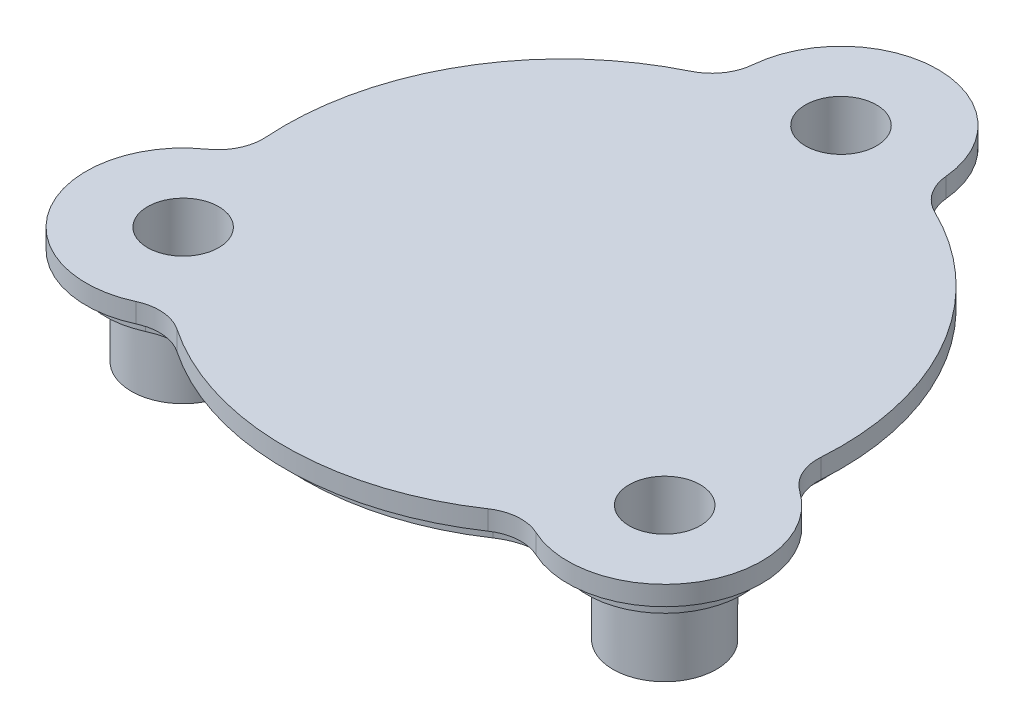
SolidWorks part; units mm, degrees
material "PE Low/Medium Density"
ref_plane "Front Plane" through (0, 0, 0) normal (0, 0, 1) x (1, 0, 0)
ref_plane "Top Plane" through (0, 0, 0) normal (0, 1, 0) x (1, 0, 0)
ref_plane "Right Plane" through (0, 0, 0) normal (1, 0, 0) x (0, 0, -1)
sketch "Sketch1" plane through (0, 0, 0) normal (0, 1, 0) x (1, 0, 0)
  line L0 (0, 0) -> (0, 57) construction
  line L1 (37.2391, 21.5) -> (0, 0) construction
  circle A0 centre (0, 43) radius 5.5
  arc A1 (-14.9415, 44.324) -> (14.9415, 44.324) centre (0, 43) cw
  arc A2 (14.9415, 44.324) -> (18.8462, 38.65) centre (21.9141, 44.9419) ccw
  arc A3 (18.8462, 38.65) -> (37.2391, 21.5) centre (0, 0) cw
  circle A4 centre (0, 43) radius 8
  circle A5 centre (0, 43) radius 3
  arc A6 (-18.8462, 38.65) -> (-37.2391, 21.5) centre (0, 0) ccw
  arc A7 (-14.9415, 44.324) -> (-18.8462, 38.65) centre (-21.9141, 44.9419) cw
  circle A8 centre (37.2391, -21.5) radius 3
  circle A9 centre (37.2391, -21.5) radius 5.5
  circle A10 centre (37.2391, -21.5) radius 8
  arc A11 (45.8564, -9.2223) -> (30.915, -35.1017) centre (37.2391, -21.5) cw
  arc A12 (30.915, -35.1017) -> (24.0488, -35.6462) centre (27.9637, -41.4491) ccw
  arc A13 (45.8564, -9.2223) -> (42.895, -3.0038) centre (49.8779, -3.4927) cw
  arc A14 (42.895, -3.0038) -> (37.2391, 21.5) centre (0, 0) ccw
  arc A15 (24.0488, -35.6462) -> (0, -43) centre (0, 0) cw
  circle A16 centre (-37.2391, -21.5) radius 3
  circle A17 centre (-37.2391, -21.5) radius 5.5
  circle A18 centre (-37.2391, -21.5) radius 8
  arc A19 (-30.915, -35.1017) -> (-45.8564, -9.2223) centre (-37.2391, -21.5) cw
  arc A20 (-45.8564, -9.2223) -> (-42.895, -3.0038) centre (-49.8779, -3.4927) ccw
  arc A21 (-30.915, -35.1017) -> (-24.0488, -35.6462) centre (-27.9637, -41.4491) cw
  arc A22 (-24.0488, -35.6462) -> (0, -43) centre (0, 0) ccw
  arc A23 (-42.895, -3.0038) -> (-37.2391, 21.5) centre (0, 0) cw
  point P65 (0, 0)
  dimension "D1" = 11
  dimension "D2" = 16
  dimension "D3" = 15
  dimension "D4" = 7
  dimension "D8" = 6
  dimension "D9" = 3
extrude "Boss-Extrude1" add sketch "Sketch1" along normal blind 6 contours A17 A16 | A18 A17 | A9 A8 | A10 A9 | A0 A5 | A4 A0 region at (-5.3444, 0, -43) region at (-7.7737, 0, -43) region at (31.8947, 0, 21.5) region at (29.4654, 0, 21.5) region at (-42.5835, 0, 21.5) region at (-45.0128, 0, 21.5)
extrude "Boss-Extrude3" add sketch "Sketch1<4>" against normal blind 3 from offset 18 separate body contours A23 A20 A19 A21 A22 A15 A12 A11 A13 A14 A3 A2 A1 A7 A6 A18 A10 A4 | A18 A17 | A10 A9 | A4 A0 region at (0, 0, 0) region at (-7.7737, 0, -43) region at (29.4654, 0, 21.5) region at (-45.0128, 0, 21.5)
sketch "Sketch1<4>" plane through (0, 0, 0) normal (0, 1, 0) x (1, 0, 0) same geometry as "Sketch1"
extrude "Boss-Extrude2" add sketch "Sketch1<3>" along normal up to surface (18 mm away) contours A18 A17 | A10 A9 | A4 A0 region at (-7.7737, 0, -43) region at (29.4654, 0, 21.5) region at (-45.0128, 0, 21.5) up to face at (0, 18, 0)
sketch "Sketch1<3>" plane through (0, 0, 0) normal (0, 1, 0) x (1, 0, 0) same geometry as "Sketch1"
sketch "Sketch2" plane through (0, 15, 0) normal (0, -1, 0) x (1, 0, 0)
  circle A20 centre (0, -43) radius 8 construction
  circle A21 centre (37.2391, 21.5) radius 8 construction
  circle A22 centre (-37.2391, 21.5) radius 8 construction
  circle A25 centre (0, -43) radius 8
  circle A26 centre (37.2391, 21.5) radius 8
  circle A27 centre (-37.2391, 21.5) radius 8
  arc A40 (-39.9023, 2.7942) -> (-17.5313, -35.9535) centre (0, 0) ccw
  arc A41 (-11.9532, -44.0592) -> (-17.5313, -35.9535) centre (-21.9141, -44.9419) ccw
  arc A42 (-11.9532, -44.0592) -> (11.9532, -44.0592) centre (0, -43) ccw
  arc A43 (17.5313, -35.9535) -> (11.9532, -44.0592) centre (21.9141, -44.9419) ccw
  arc A44 (17.5313, -35.9535) -> (39.9023, 2.7942) centre (0, 0) ccw
  arc A45 (44.133, 11.6779) -> (39.9023, 2.7942) centre (49.8779, 3.4927) ccw
  arc A46 (44.133, 11.6779) -> (32.1798, 32.3813) centre (37.2391, 21.5) ccw
  arc A47 (22.371, 33.1593) -> (32.1798, 32.3813) centre (27.9637, 41.4491) ccw
  arc A48 (22.371, 33.1593) -> (-22.371, 33.1593) centre (0, 0) ccw
  arc A49 (-32.1798, 32.3813) -> (-22.371, 33.1593) centre (-27.9637, 41.4491) ccw
  arc A50 (-32.1798, 32.3813) -> (-44.133, 11.6779) centre (-37.2391, 21.5) ccw
  arc A51 (-39.9023, 2.7942) -> (-44.133, 11.6779) centre (-49.8779, 3.4927) ccw
  arc A60 (-39.9023, 2.7942) -> (-17.5313, -35.9535) centre (0, 0) ccw
  arc A61 (-11.9532, -44.0592) -> (-17.5313, -35.9535) centre (-21.9141, -44.9419) ccw
  arc A62 (-11.9532, -44.0592) -> (11.9532, -44.0592) centre (0, -43) ccw
  arc A63 (17.5313, -35.9535) -> (11.9532, -44.0592) centre (21.9141, -44.9419) ccw
  arc A64 (17.5313, -35.9535) -> (39.9023, 2.7942) centre (0, 0) ccw
  arc A65 (44.133, 11.6779) -> (39.9023, 2.7942) centre (49.8779, 3.4927) ccw
  arc A66 (44.133, 11.6779) -> (32.1798, 32.3813) centre (37.2391, 21.5) ccw
  arc A67 (22.371, 33.1593) -> (32.1798, 32.3813) centre (27.9637, 41.4491) ccw
  arc A68 (22.371, 33.1593) -> (-22.371, 33.1593) centre (0, 0) ccw
  arc A69 (-32.1798, 32.3813) -> (-22.371, 33.1593) centre (-27.9637, 41.4491) ccw
  arc A70 (-32.1798, 32.3813) -> (-44.133, 11.6779) centre (-37.2391, 21.5) ccw
  arc A71 (-39.9023, 2.7942) -> (-44.133, 11.6779) centre (-49.8779, 3.4927) ccw
  dimension "D1" = 3
extrude "Boss-Extrude4" add sketch "Sketch2" along normal blind 3
equation "\"B\"= 18"
equation "\"D19@Boss-Extrude3\"=\"B\""
equation "\"A\"=43"
equation "\"D7@Sketch1\"=\"A\""
equation "\"D5@Sketch1\"=\"A\""
equation "\"C\"= 3"
equation "\"D1@Boss-Extrude1\"=\"C\"*2"
equation "\"D1@Boss-Extrude3\"=\"C\""
equation "\"D1@Sketch2\"=\"C\""
equation "\"D1@Boss-Extrude4\"=\"C\""
